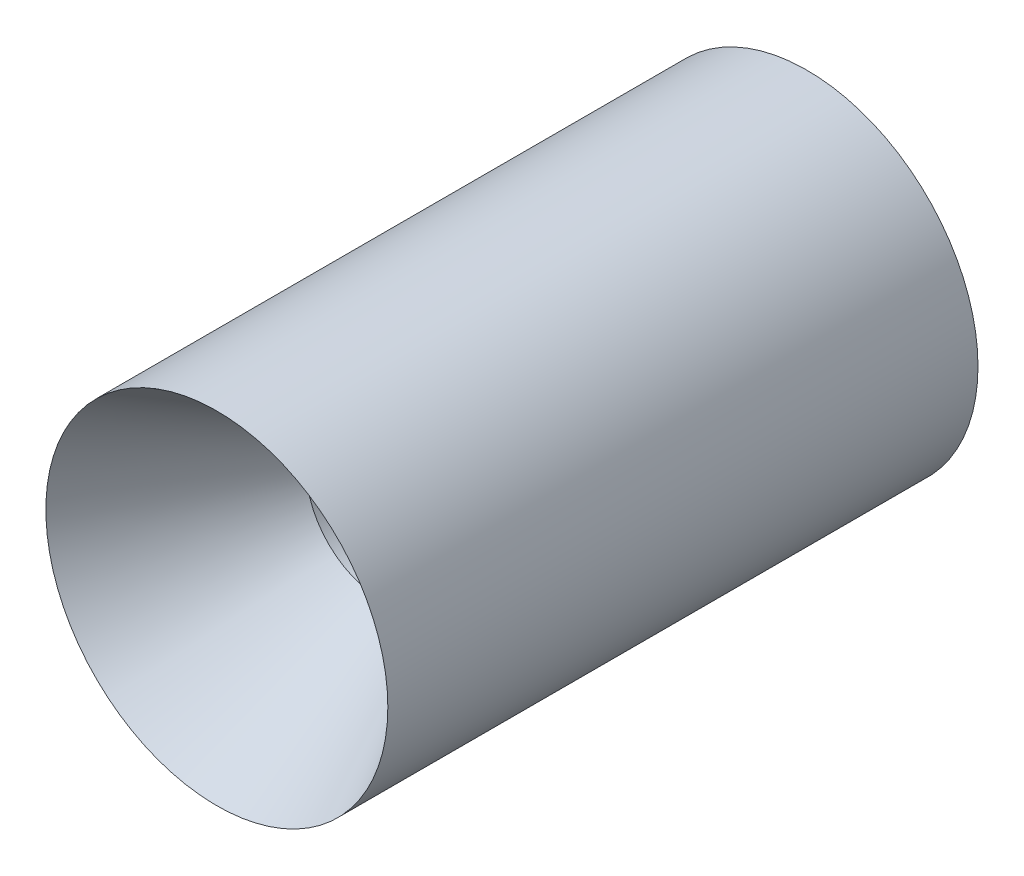
SolidWorks part; units mm, degrees
material "C (Graphite)"
ref_plane "Front Plane" through (0, 0, 0) normal (0, 0, 1) x (1, 0, 0)
ref_plane "Top Plane" through (0, 0, 0) normal (0, 1, 0) x (1, 0, 0)
ref_plane "Right Plane" through (0, 0, 0) normal (1, 0, 0) x (0, 0, -1)
sketch "Sketch3" plane through (0, 0, 0) normal (1, 0, 0) x (0, 0, -1)
  line L0 (0, 0) -> (77.1711, 0) construction
  line L5 (49.53, 12.7208) -> (49.53, 14.351)
  line L6 (49.53, 14.351) -> (0, 14.351)
  line L9 (19.5576, 6.35) -> (13.8581, 6.35)
  line L11 (0, 14.351) -> (13.8581, 6.35)
  line L12 (19.5576, 6.35) -> (49.53, 12.7208)
  point P3 (0, 0)
  point P4 (17.7153, 5.9584)
  dimension "D1" = 12.7208
  dimension "D2" = 30
  dimension "D3" = 12
  dimension "D4" = 49.53
  dimension "D5" = 6.35
  dimension "D7" = 14.351
revolve "Revolve1" add sketch "Sketch3" angle 360 about L0
